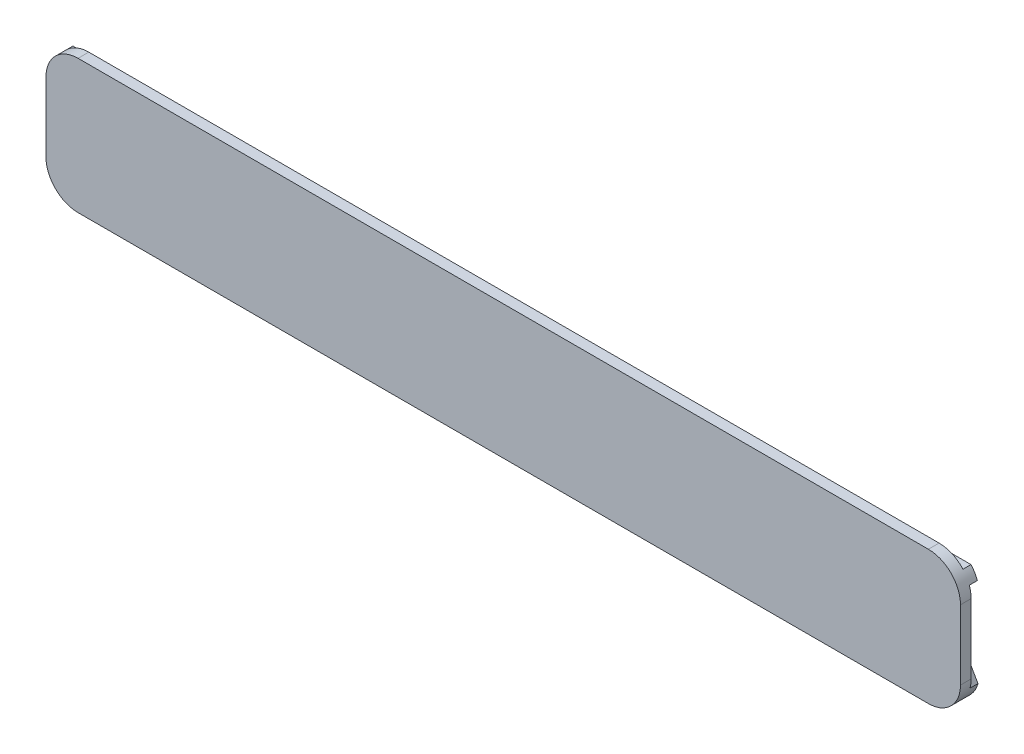
SolidWorks part; units mm, degrees
ref_plane "Front Plane" through (0, 0, 0) normal (0, 0, 1) x (1, 0, 0)
ref_plane "Top Plane" through (0, 0, 0) normal (0, 1, 0) x (1, 0, 0)
ref_plane "Right Plane" through (0, 0, 0) normal (1, 0, 0) x (0, 0, -1)
sketch "Sketch1" plane through (0, 0, 0) normal (0, 0, 1) x (1, 0, 0)
  line L0 (0, 0) -> (55.7, 0) construction
  line L1 (-57.65, 12.5) -> (113.35, 12.5)
  line L2 (-57.65, 12.5) -> (-57.65, -12.5)
  line L3 (-57.65, -12.5) -> (113.35, -12.5)
  line L4 (113.35, 12.5) -> (113.35, -12.5)
  circle A0 centre (55.7, 0) radius 3 construction
  circle A1 centre (0, 0) radius 3 construction
  circle A2 centre (55.7, 0) radius 3 construction
  circle A3 centre (0, 0) radius 3 construction
  circle A4 centre (0, 0) radius 3.2
  circle A5 centre (55.7, 0) radius 3.2
  point P14 (27.85, 0)
  point P15 (27.85, 12.5)
  point P16 (113.35, 0)
  point P17 (0, 0)
  dimension "D2" = 25
  dimension "D3" = 171
  dimension "D1" = 0.2
extrude "Boss-Extrude1" add sketch "Sketch1" against normal blind 1
sketch "Sketch2" plane through (0, 0, 0) normal (0, 0, 1) x (1, 0, 0)
  line L4 (-57.65, 12.5) -> (-57.65, -12.5)
  line L5 (-57.65, -12.5) -> (113.35, -12.5)
  line L6 (113.35, -12.5) -> (113.35, 12.5)
  line L7 (113.35, 12.5) -> (-57.65, 12.5)
  line L8 (-57.65, 12.5) -> (-57.65, -12.5)
  line L9 (-57.65, -12.5) -> (113.35, -12.5)
  line L10 (113.35, -12.5) -> (113.35, 12.5)
  line L11 (113.35, 12.5) -> (-57.65, 12.5)
  dimension "D1" = 0
extrude "Boss-Extrude2" add sketch "Sketch2" along normal blind 1
sketch "Sketch6" plane through (0, 0, -1) normal (0, 0, -1) x (-1, 0, 0)
  circle A0 centre (0, 0) radius 3.2 construction
  circle A1 centre (-55.7, 0) radius 3.2 construction
  circle A2 centre (0, 0) radius 3.2
  circle A3 centre (-55.7, 0) radius 3.2
  circle A4 centre (-55.7, 0) radius 5.2
  circle A5 centre (0, 0) radius 5.2
  dimension "D1" = 2
extrude "Boss-Extrude5" add sketch "Sketch6" along normal blind 2.5
sketch "Sketch5" plane through (0, 0, -1) normal (0, 0, -1) x (-1, 0, 0)
  line L0 (-105.35, 0) -> (49894.65, 0) construction
  line L1 (-113.35, -12.5) -> (-113.35, 12.5) construction
  line L2 (57.65, 12.5) -> (57.65, -12.5) construction
  line L3 (-27.85, -10.5) -> (-27.85, -8.5)
  line L4 (-113.35, 10.5) -> (-27.85, 10.5)
  line L5 (-113.35, 10.5) -> (-113.35, 8.5)
  line L6 (-113.35, 8.5) -> (-103.535, 8.5)
  line L7 (-27.85, 10.5) -> (-27.85, 8.5)
  line L8 (-111.0406, -8.5) -> (-89.4107, -8.5)
  line L9 (-113.35, -10.5) -> (-113.35, -8.5)
  line L10 (-113.35, -10.5) -> (-27.85, -10.5)
  line L11 (-113.35, 12.5) -> (57.65, 12.5) construction
  line L12 (-113.35, -8.5) -> (-103.535, 8.5)
  line L13 (-101.2256, 8.5) -> (-99.2256, 8.5)
  line L14 (-96.9162, 8.5) -> (-87.1013, -8.5)
  line L15 (-87.1013, -8.5) -> (-85.1013, -8.5)
  line L16 (-82.7919, -8.5) -> (-72.9769, 8.5)
  line L17 (-111.0406, -8.5) -> (-101.2256, 8.5)
  line L18 (-101.2256, 8.5) -> (-99.2256, 8.5)
  line L19 (-99.2256, 8.5) -> (-89.4107, -8.5)
  line L20 (-85.1013, -8.5) -> (-75.2863, 8.5)
  line L21 (-40.9744, 8.5) -> (-31.1594, -8.5)
  line L23 (-28.85, -8.5) -> (-38.665, 8.5)
  line L25 (-101.2256, 8.5) -> (-99.2256, 8.5)
  line L26 (-96.9162, 8.5) -> (-75.2863, 8.5)
  line L27 (-87.1013, -8.5) -> (-85.1013, -8.5)
  line L28 (-82.7919, -8.5) -> (-49.6, -8.5)
  line L29 (-72.9769, 8.5) -> (-45.0449, 8.5)
  line L30 (-38.665, 8.5) -> (-27.85, 8.5)
  line L31 (-28.85, -8.5) -> (-27.85, -8.5)
  line L32 (-45.0449, 8.5) -> (-49.6, -8.5)
  line L34 (-47.5295, -8.5) -> (-42.9744, 8.5)
  line L35 (-42.9744, 8.5) -> (-40.9744, 8.5)
  line L36 (-47.5295, -8.5) -> (-31.1594, -8.5)
  point P4 (-113.35, 0)
  point P7 (57.65, 0)
  point P34 (-27.85, 12.5)
  line M32 (-113.35, 12.5) -> (-113.35, -12.5)
  dimension "D1" = 2
  dimension "D2" = 2
  dimension "D3" = 2
  dimension "D4" = 2
  dimension "D5" = 2
  dimension "D6" = 2
  dimension "D7" = 60
  dimension "D8" = 2
  dimension "D9" = 1
  dimension "D10" = 2
  dimension "D11" = 45
extrude "Boss-Extrude4" add sketch "Sketch5" along normal blind 1.5 contours L12 L0 L17 L13 L19 L14 L26 L20 L16 L29 L21 L23 L30 L7 L4 L6 M32 | L0 L12 L10 L3 L31 L23 L21 L28 L16 L20 L15 L14 L19 L8 L17 M32 region at (32.0662, -4.6902, -1)
ref_plane "Plane1" through (27.85, 0, 0) normal (1, 0, 0) x (0, 0, -1)
mirror "Mirror1" about plane through (27.85, 0, 0) normal (1, 0, 0) of "Boss-Extrude4"
fillet "Fillet1" radius 6 4 edges at (113.35, 12.5, 0) (113.35, -12.5, 0) (-57.65, -12.5, 0) (-57.65, 12.5, 0)
sketch "Sketch3" plane through (0, 0, 1) normal (0, 0, 1) x (1, 0, 0)
  line L0 (-57.65, -5) -> (113.35, -5) construction
  line L1 (-51.65, -12.5) -> (107.35, -12.5) construction
  line L2 (-57.65, 6.5) -> (-57.65, -6.5) construction
  text T0 "ED Robotics" font "Century Gothic" height 10
  point P7 (27.85, -12.5)
  point P8 (27.85, -5)
  dimension "D1" = 5
extrude "Engraved team name" [suppressed] cut sketch "Sketch3" against normal blind 0.5
equation "\"D3@Sketch5\"=\"D1@Sketch5\""
equation "\"D4@Sketch5\"=\"D3@Sketch5\""
equation "\"D5@Sketch5\"=\"D3@Sketch5\""
equation "\"D6@Sketch5\"=\"D3@Sketch5\""
equation "\"D8@Sketch5\"=\"D3@Sketch5\""
equation "\"D9@Sketch5\"=\"D3@Sketch5\"/2"
equation "\"D10@Sketch5\"=\"D3@Sketch5\""
